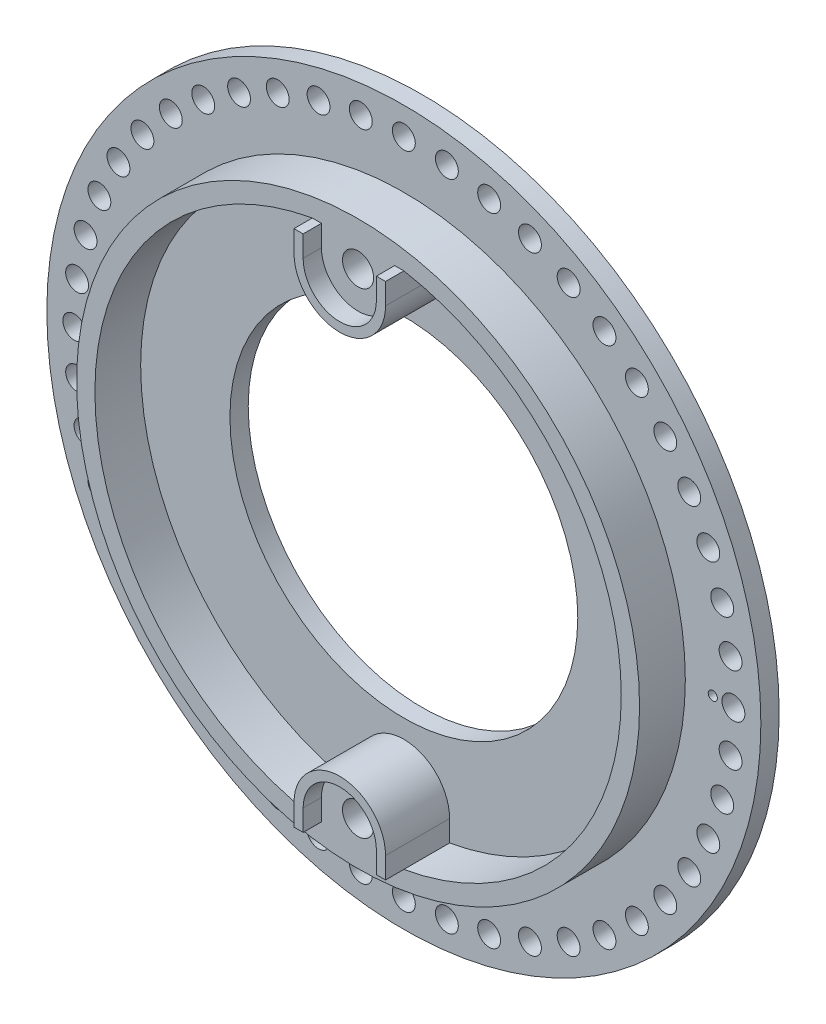
SolidWorks part; units mm, degrees
ref_plane "Front Plane" through (0, 0, 0) normal (0, 0, 1) x (1, 0, 0)
ref_plane "Top Plane" through (0, 0, 0) normal (0, 1, 0) x (1, 0, 0)
ref_plane "Right Plane" through (0, 0, 0) normal (1, 0, 0) x (0, 0, -1)
sketch "Sketch1" plane through (0, 0, 0) normal (0, 0, 1) x (1, 0, 0)
  circle A0 centre (0, 0) radius 39
  dimension "D1" = 78
extrude "Boss-Extrude1" add sketch "Sketch1" along normal blind 2
sketch "Sketch3" plane through (0, 0, 2) normal (0, 0, 1) x (1, 0, 0)
  line L0 (-5, 26) -> (-5, 28.3119)
  line L1 (5, 26) -> (5, 28.3119)
  line L2 (5, -26) -> (5, -28.3119)
  line L3 (-5, -26) -> (-5, -28.3119)
  circle A0 centre (0, 0) radius 30.75
  arc A1 (-5, 28.3119) -> (-5, -28.3119) centre (0, 0) ccw
  arc A2 (-5, 26) -> (5, 26) centre (0, 26) ccw
  circle A3 centre (0, 0) radius 28.75 construction
  arc A4 (5, -26) -> (-5, -26) centre (0, -26) ccw
  arc A5 (5, -28.3119) -> (5, 28.3119) centre (0, 0) ccw
  point P18 (0, 0)
  point P22 (-0.2453, 0)
  dimension "D1" = 61.5
  dimension "D3" = 10
  dimension "D5" = 2
  dimension "D4" = 26
  dimension "D2" = 2
extrude "Boss-Extrude2" add sketch "Sketch3" along normal blind 5 contours A1 L3 A4 L2 A5 L1 A2 L0 | A0
sketch "Sketch5" plane through (0, 0, 7) normal (0, 0, 1) x (1, 0, 0)
  circle A0 centre (0, -26) radius 1.7
  circle A1 centre (0, 26) radius 1.7
  point P7 (0, 0)
  dimension "D1" = 26
  dimension "D2" = 3.4
  dimension "D3" = 2
  dimension "D4" = 52
extrude "Cut-Extrude2" cut sketch "Sketch5" against normal up to surface (7 mm away) up to face at (39, 0, 0)
sketch "Sketch6" plane through (0, 0, 0) normal (0, 0, -1) x (-1, 0, 0)
  circle A0 centre (0, 26) radius 3
  circle A1 centre (0, -26) radius 3
  dimension "D1" = 6
  dimension "D2" = 6
  dimension "D3" = 26
  dimension "D4" = 26
extrude "Cut-Extrude3" cut sketch "Sketch6" against normal blind 4.5
sketch "Sketch7" plane through (0, 0, 0) normal (0, 0, -1) x (-1, 0, 0)
  circle A0 centre (0, 0) radius 19
  dimension "D1" = 38
extrude "Cut-Extrude4" cut sketch "Sketch7" against normal up to surface (2 mm away) up to face at (0, 0, 2)
sketch "Sketch8" plane through (0, 0, 2) normal (0, 0, 1) x (1, 0, 0)
  circle A0 centre (36, 0) radius 1.25
  circle A1 centre (35.692, -4.6989) radius 1.25
  circle A2 centre (34.7733, -9.3175) radius 1.25
  circle A3 centre (33.2597, -13.7766) radius 1.25
  circle A4 centre (31.1769, -18) radius 1.25
  circle A5 centre (28.5607, -21.9154) radius 1.25
  circle A6 centre (25.4558, -25.4558) radius 1.25
  circle A7 centre (21.9154, -28.5607) radius 1.25
  circle A8 centre (18, -31.1769) radius 1.25
  circle A9 centre (13.7766, -33.2597) radius 1.25
  circle A10 centre (9.3175, -34.7733) radius 1.25
  circle A11 centre (4.6989, -35.692) radius 1.25
  circle A12 centre (0, -36) radius 1.25
  circle A13 centre (-4.6989, -35.692) radius 1.25
  circle A14 centre (-9.3175, -34.7733) radius 1.25
  circle A15 centre (-13.7766, -33.2597) radius 1.25
  circle A16 centre (-18, -31.1769) radius 1.25
  circle A17 centre (-21.9154, -28.5607) radius 1.25
  circle A18 centre (-25.4558, -25.4558) radius 1.25
  circle A19 centre (-28.5607, -21.9154) radius 1.25
  circle A20 centre (-31.1769, -18) radius 1.25
  circle A21 centre (-33.2597, -13.7766) radius 1.25
  circle A22 centre (-34.7733, -9.3175) radius 1.25
  circle A23 centre (-35.692, -4.6989) radius 1.25
  circle A24 centre (-36, 0) radius 1.25
  circle A25 centre (-35.692, 4.6989) radius 1.25
  circle A26 centre (-34.7733, 9.3175) radius 1.25
  circle A27 centre (-33.2597, 13.7766) radius 1.25
  circle A28 centre (-31.1769, 18) radius 1.25
  circle A29 centre (-28.5607, 21.9154) radius 1.25
  circle A30 centre (-25.4558, 25.4558) radius 1.25
  circle A31 centre (-21.9154, 28.5607) radius 1.25
  circle A32 centre (-18, 31.1769) radius 1.25
  circle A33 centre (-13.7766, 33.2597) radius 1.25
  circle A34 centre (-9.3175, 34.7733) radius 1.25
  circle A35 centre (-4.6989, 35.692) radius 1.25
  circle A36 centre (0, 36) radius 1.25
  circle A37 centre (4.6989, 35.692) radius 1.25
  circle A38 centre (9.3175, 34.7733) radius 1.25
  circle A39 centre (13.7766, 33.2597) radius 1.25
  circle A40 centre (18, 31.1769) radius 1.25
  circle A41 centre (21.9154, 28.5607) radius 1.25
  circle A42 centre (25.4558, 25.4558) radius 1.25
  circle A43 centre (28.5607, 21.9154) radius 1.25
  circle A44 centre (31.1769, 18) radius 1.25
  circle A45 centre (33.2597, 13.7766) radius 1.25
  circle A46 centre (34.7733, 9.3175) radius 1.25
  circle A47 centre (35.692, 4.6989) radius 1.25
  point P104 (0, 0)
  dimension "D1" = 36
  dimension "D2" = 2.5
  dimension "D3" = 48
extrude "Cut-Extrude5" cut sketch "Sketch8" against normal up to surface (2 mm away) up to face at (-19, 0, 0)
fillet "Fillet1" radius 1.5 2 edges at (-3, -26, 4.5) (-3, 26, 4.5)
sketch "Sketch9" plane through (0, 0, 7) normal (0, 0, 1) x (1, 0, 0)
  line L2 (-4, 28.3119) -> (-5, 28.3119)
  line L3 (4, 28.3119) -> (5, 28.3119)
  line L4 (4, 28.3119) -> (4, 26)
  line L5 (-4, 26) -> (-4, 28.3119)
  line L6 (4, 28.3119) -> (4, 26)
  line L7 (-4, 26) -> (-4, 28.3119)
  line L8 (-5, 28.3119) -> (-5, 26)
  line L9 (5, 26) -> (5, 28.3119)
  line L10 (-5, -26) -> (-5, -28.3119)
  line L11 (-4, -28.3119) -> (-5, -28.3119)
  line L12 (-4, -28.3119) -> (-4, -26)
  line L13 (4, -26) -> (4, -28.3119)
  line L14 (4, -28.3119) -> (5, -28.3119)
  line L15 (5, -28.3119) -> (5, -26)
  arc A2 (4, -26) -> (-4, -26) centre (0, -26) ccw
  arc A4 (-5, 26) -> (5, 26) centre (0, 26) ccw
  arc A5 (-4, 26) -> (4, 26) centre (0, 26) ccw
  arc A6 (-4, 26) -> (4, 26) centre (0, 26) ccw
  arc A8 (5, -26) -> (-5, -26) centre (0, -26) ccw
  point P26 (0, 0)
  dimension "D1" = 2
  dimension "D2" = 1
extrude "Boss-Extrude3" add sketch "Sketch9" along normal blind 2
sketch "Alignment_Hole" plane through (0, 0, 0) normal (0, 0, -1) x (-1, 0, 0)
  circle A0 centre (-33.75, 0) radius 0.5
  circle A2 centre (-36, 0) radius 1.25 construction
  point P2 (0, 0)
  point P4 (0, 0)
  point P5 (0, 0)
  point P7 (0, 0)
  dimension "D1" = 1
  dimension "D2" = 2.25
extrude "Alignment_Hole - Cut" cut sketch "Alignment_Hole" against normal through all both and the other way through all
equation "\"D2@Sketch6\"=\"D1@Sketch6\""
